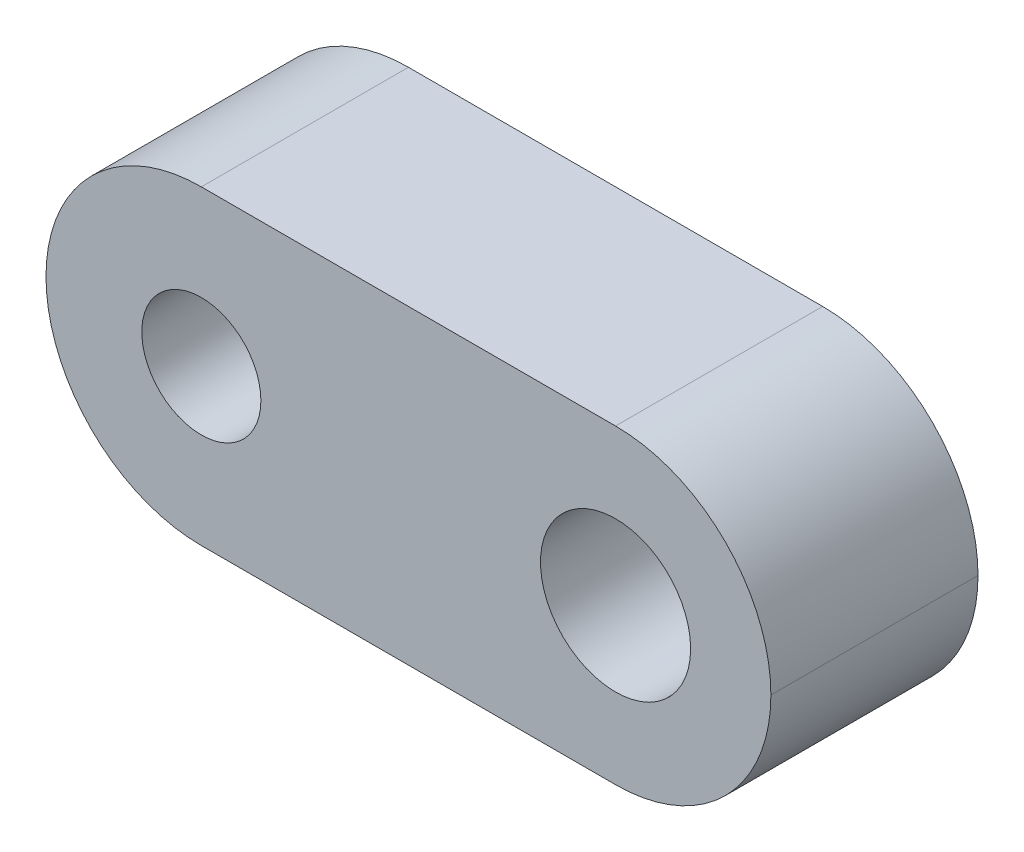
SolidWorks part; units mm, degrees
ref_plane "Front" through (0, 0, 0) normal (0, 0, 1) x (1, 0, 0)
ref_plane "Top" through (0, 0, 0) normal (0, 1, 0) x (1, 0, 0)
ref_plane "Right" through (0, 0, 0) normal (1, 0, 0) x (0, 0, -1)
sketch "Sketch1" plane through (0, 0, 0) normal (0, 0, 1) x (1, 0, 0)
  line L1 (0, 0) -> (14, 0)
  line L2 (0, 0) -> (0, -6)
  line L3 (0, -6) -> (14, -6)
  line L4 (14, 0) -> (14, -6)
  dimension "D1" = 6
  dimension "D2" = 14
extrude "Boss-Extrude1" add sketch "Sketch1" along normal blind 4
sketch "Sketch2" plane through (0, 0, 4) normal (0, 0, 1) x (1, 0, 0)
  line L0 (0, 0) -> (0, -6) construction
  line L1 (14, -6) -> (14, 0) construction
  circle A0 centre (3, -3) radius 1.15
  circle A1 centre (11, -3) radius 1.45
  dimension "D1" = 2.3
  dimension "D3" = 2.9
  dimension "D2" = 3
  dimension "D4" = 3
extrude "Cut-Extrude1" cut sketch "Sketch2" against normal through all and the other way through all
fillet "Fillet1" radius 3 4 edges at (14, -6, 2) (14, 0, 2) (0, -6, 2) (0, 0, 2)
